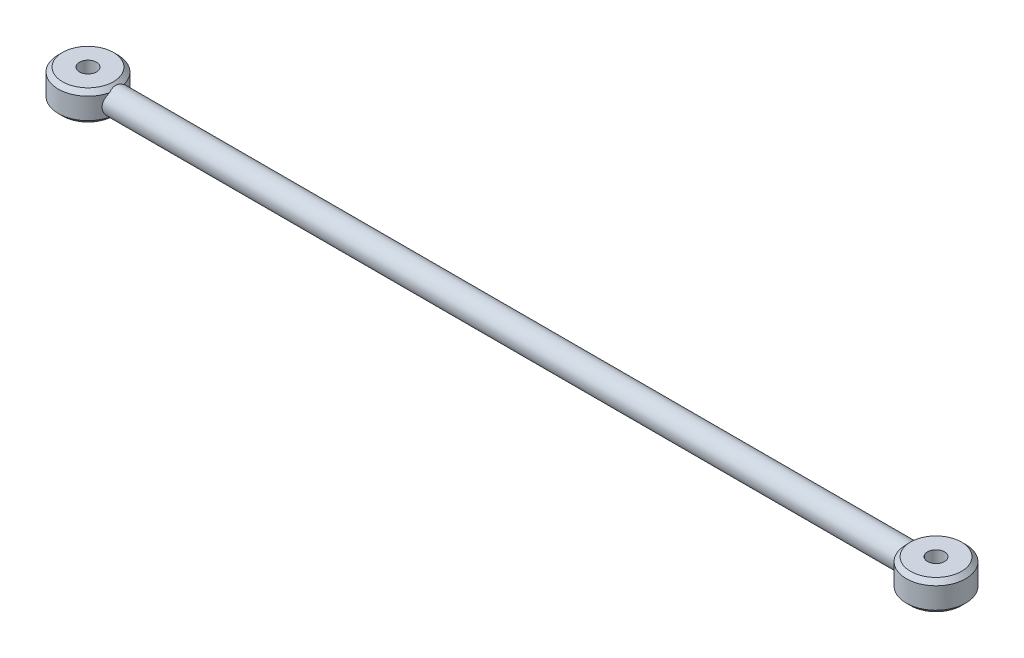
SolidWorks part; units mm, degrees
ref_plane "Front Plane" through (0, 0, 0) normal (0, 0, 1) x (1, 0, 0)
ref_plane "Top Plane" through (0, 0, 0) normal (0, 1, 0) x (1, 0, 0)
ref_plane "Right Plane" through (0, 0, 0) normal (1, 0, 0) x (0, 0, -1)
sketch "Sketch1" plane through (0, 0, 0) normal (0, 1, 0) x (1, 0, 0)
  line L0 (0, 0) -> (200, 0) construction
  circle A0 centre (0, 0) radius 7
  circle A1 centre (200, 0) radius 7
  circle A2 centre (0, 0) radius 2
  circle A3 centre (200, 0) radius 2
  dimension "D2" = 4
  dimension "D5" = 14
  dimension "D1" = 200
extrude "Boss-Extrude1" add sketch "Sketch1" along normal blind 7
ref_plane "Plane1" through (150, 0, 0) normal (1, 0, 0) x (0, 0, -1)
ref_plane "Plane2" through (22.5, 0, 0) normal (1, 0, 0) x (0, 0, -1)
sketch "Sketch2" plane through (22.5, 0, 0) normal (1, 0, 0) x (0, 0, -1)
  line L0 (0, 0) -> (0, 3.5) construction
  circle A0 centre (0, 3.5) radius 3
  dimension "D2" = 6
  dimension "D1" = 3.5
extrude "Boss-Extrude2" add sketch "Sketch2" along normal up to surface and the other way up to surface up to face at (200, 7, 7) other way up to face at (0, 7, 7)
chamfer "Chamfer1" distance 1 angle 45 4 edges at (0, 0, 7) (0, 7, 7) (200, 0, 7) (200, 7, 7)
